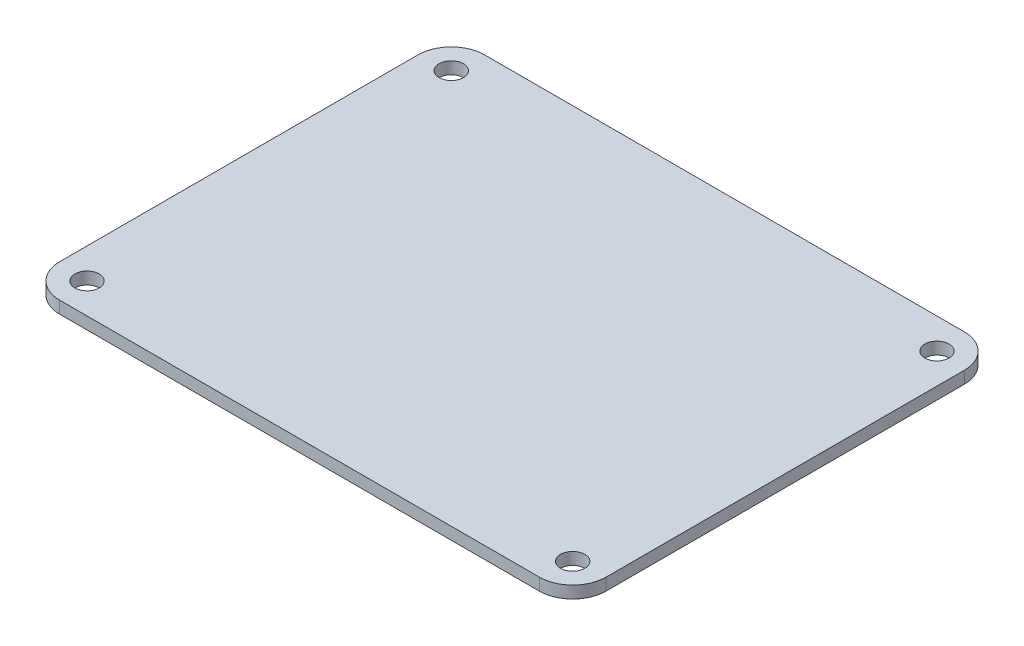
SolidWorks part; units mm, degrees
ref_plane "Front Plane" through (0, 0, 0) normal (0, 0, 1) x (1, 0, 0)
ref_plane "Top Plane" through (0, 0, 0) normal (0, 1, 0) x (1, 0, 0)
ref_plane "Right Plane" through (0, 0, 0) normal (1, 0, 0) x (0, 0, -1)
sketch "Sketch1" plane through (0, 0, 0) normal (0, 1, 0) x (1, 0, 0)
  line L1 (-114.3, 88.9) -> (114.3, 88.9)
  line L2 (-114.3, 88.9) -> (-114.3, -88.9)
  line L3 (-114.3, -88.9) -> (114.3, -88.9)
  line L4 (114.3, 88.9) -> (114.3, -88.9)
  line L5 (-114.3, 88.9) -> (114.3, -88.9) construction
  line L6 (-114.3, -88.9) -> (114.3, 88.9) construction
  point P0 (0, 0)
  dimension "D1" = 177.8
  dimension "10" = 228.6
extrude "Boss-Extrude1" add sketch "Sketch1" along normal blind 5.08
sketch "Sketch2" plane through (0, 5.08, 0) normal (0, 1, 0) x (1, 0, 0)
  line L0 (-101.6, 76.2) -> (-101.6, 88.9) construction
  line L1 (114.3, 88.9) -> (-114.3, 88.9) construction
  line L2 (-101.6, 76.2) -> (-114.3, 76.2) construction
  line L3 (-114.3, 88.9) -> (-114.3, -88.9) construction
  line L4 (-101.6, -76.2) -> (-114.3, -76.2) construction
  line L5 (-101.6, -76.2) -> (-101.6, -88.9) construction
  line L6 (-114.3, -88.9) -> (114.3, -88.9) construction
  line L7 (101.6, 76.2) -> (101.6, 88.9) construction
  line L8 (101.6, 76.2) -> (114.3, 76.2) construction
  line L9 (114.3, -88.9) -> (114.3, 88.9) construction
  line L10 (101.6, -76.2) -> (101.6, -88.9) construction
  line L11 (101.6, -76.2) -> (114.3, -76.2) construction
  circle A0 centre (-101.6, 76.2) radius 5.08
  circle A1 centre (101.6, 76.2) radius 5.08
  circle A2 centre (101.6, -76.2) radius 5.08
  circle A3 centre (-101.6, -76.2) radius 5.08
  dimension "D1" = 10.16
  dimension "D2" = 12.7
extrude "Cut-Extrude1" cut sketch "Sketch2" against normal through all
fillet "Fillet3" radius 13.97 4 edges at (114.3, 2.54, -88.9) (114.3, 2.54, 88.9) (-114.3, 2.54, -88.9) (-114.3, 2.54, 88.9)
sketch "Sketch3" plane through (0, 5.08, 0) normal (0, 1, 0) x (1, 0, 0)
  line L0 (-114.3, 0) -> (114.3, 0) construction
  line L1 (-114.3, 74.93) -> (-114.3, -74.93) construction
  line L2 (114.3, -74.93) -> (114.3, 74.93) construction
  line L3 (0, 88.9) -> (0, -88.9) construction
  line L4 (100.33, 88.9) -> (-100.33, 88.9) construction
  line L5 (-100.33, -88.9) -> (100.33, -88.9) construction
  point P12 (0, 0)
